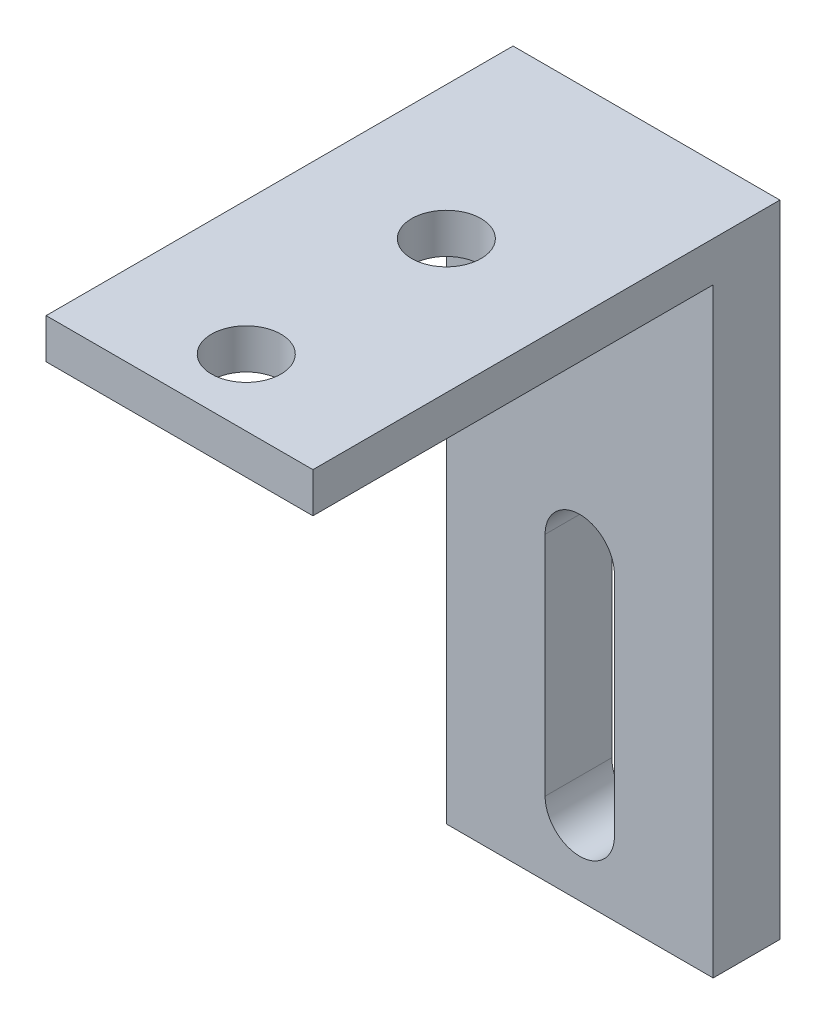
SolidWorks part; units mm, degrees
ref_plane "Front Plane" through (0, 0, 0) normal (0, 0, 1) x (1, 0, 0)
ref_plane "Top Plane" through (0, 0, 0) normal (0, 1, 0) x (1, 0, 0)
ref_plane "Right Plane" through (0, 0, 0) normal (1, 0, 0) x (0, 0, -1)
sketch "Sketch1" plane through (0, 0, 0) normal (0, 1, 0) x (1, 0, 0)
  line L1 (-10, 10) -> (10, 10)
  line L2 (-10, 10) -> (-10, -10)
  line L3 (-10, -10) -> (10, -10)
  line L4 (10, 10) -> (10, -10)
  line L5 (-10, 10) -> (10, -10) construction
  line L6 (-10, -10) -> (10, 10) construction
  circle A0 centre (0, 0) radius 2.6
  point P0 (0, 0)
  dimension "D2" = 5.2
  dimension "D1" = 20
extrude "Boss-Extrude2" add sketch "Sketch1" along normal blind 3
sketch "Sketch2" plane through (0, 0, 10) normal (0, 0, 1) x (1, 0, 0)
  line L4 (-10, 0) -> (10, 0)
  line L5 (10, 0) -> (10, 3)
  line L6 (10, 3) -> (-10, 3)
  line L7 (-10, 3) -> (-10, 0)
  line L8 (-10, 0) -> (10, 0)
  line L9 (10, 0) -> (10, 3)
  line L10 (10, 3) -> (-10, 3)
  line L11 (-10, 3) -> (-10, 0)
  dimension "D1" = 0
extrude "Boss-Extrude3" add sketch "Sketch2" along normal blind 10
sketch "Sketch4" plane through (0, 3, 0) normal (0, 1, 0) x (1, 0, 0)
  line L0 (0, 0) -> (0, -15)
  circle A0 centre (0, -15) radius 2.6
  dimension "D2" = 5.2
  dimension "D1" = 15
extrude "Cut-Extrude1" cut sketch "Sketch4" against normal blind 10 contours A0 region at (-1.7865, 3, 16.7865)
sketch "Sketch6" plane through (0, 0, -10) normal (0, 0, -1) x (-1, 0, 0)
  line L4 (-10, 0) -> (10, 0)
  line L5 (10, 0) -> (10, 3)
  line L6 (10, 3) -> (-10, 3)
  line L7 (-10, 3) -> (-10, 0)
  line L8 (-10, 0) -> (10, 0)
  line L9 (10, 0) -> (10, 3)
  line L10 (10, 3) -> (-10, 3)
  line L11 (-10, 3) -> (-10, 0)
  dimension "D1" = 0
extrude "Boss-Extrude5" add sketch "Sketch6" along normal blind 5
sketch "Sketch7" plane through (0, 0, 0) normal (0, -1, 0) x (1, 0, 0)
  line L1 (10, -15) -> (-10, -15)
  line L2 (10, -15) -> (10, -10)
  line L3 (10, -10) -> (-10, -10)
  line L4 (-10, -15) -> (-10, -10)
  line L5 (-10, -15) -> (-10, 20) construction
  dimension "D1" = 5
  dimension "D2" = 20
extrude "Boss-Extrude6" add sketch "Sketch7" along normal blind 45
sketch "Sketch8" plane through (0, 0, -15) normal (0, 0, -1) x (-1, 0, 0)
  line L0 (0, 0) -> (0, -45) construction
  line L1 (10, -45) -> (-10, -45) construction
  line L2 (-2.6, -22.5) -> (-2.6, -39.5)
  line L3 (2.6, -22.5) -> (2.6, -39.5)
  arc A0 (2.6, -22.5) -> (-2.6, -22.5) centre (0, -22.5) ccw
  arc A1 (-2.6, -39.5) -> (2.6, -39.5) centre (0, -39.5) ccw
  dimension "D1" = 5.2
  dimension "D2" = 5.2
  dimension "D4" = 17
extrude "Cut-Extrude2" cut sketch "Sketch8" against normal blind 5 contours L2 A1 L3 A0
